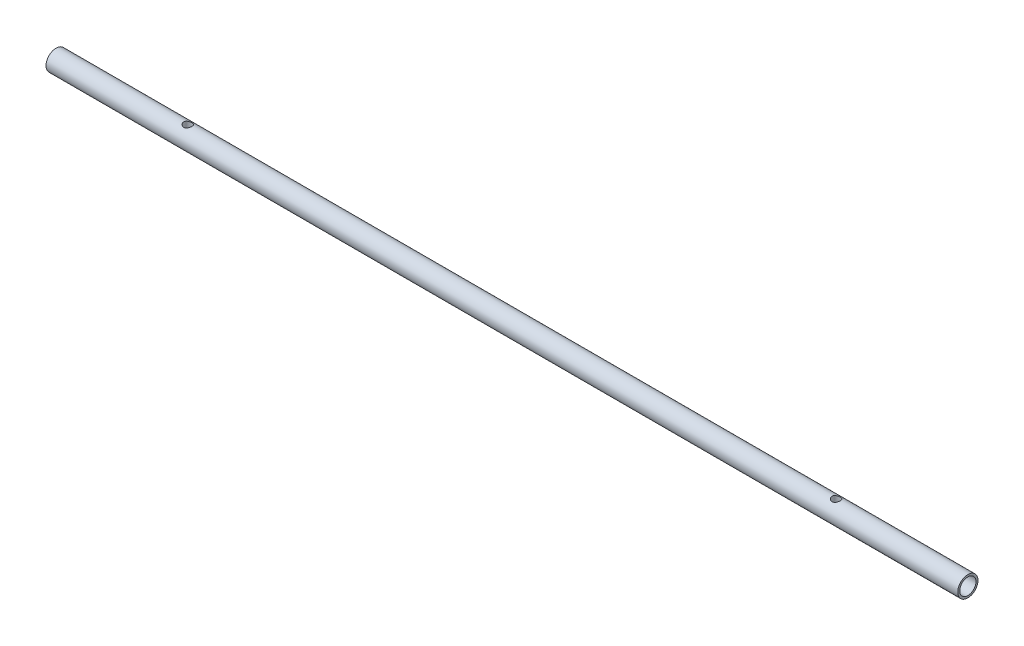
SolidWorks part; units mm, degrees
ref_plane "Front Plane" through (0, 0, 0) normal (1, 0, 0) x (0, 1, 0)
ref_plane "Top Plane" through (0, 0, 0) normal (0, 0, 1) x (0, 1, 0)
ref_plane "Right Plane" through (0, 0, 0) normal (0, 1, 0) x (-1, 0, 0)
sketch "Sketch1" plane through (0, 0, 0) normal (1, 0, 0) x (0, 1, 0)
  circle A0 centre (0, 0) radius 10
  dimension "D1" = 20
extrude "Boss-Extrude1" add sketch "Sketch1" along normal blind 900
sketch "Sketch2" plane through (900, 0, 0) normal (1, 0, 0) x (0, 1, 0)
  circle A0 centre (0, 0) radius 8
  dimension "D1" = 16
extrude "Cut-Extrude1" cut sketch "Sketch2" against normal blind 40
sketch "Sketch3" plane through (0, 0, 0) normal (-1, 0, 0) x (0, -1, 0)
  circle A0 centre (0, 0) radius 8
  dimension "D1" = 16
extrude "Cut-Extrude2" cut sketch "Sketch3" against normal blind 40
sketch "Sketch4" plane through (0, 0, 0) normal (0, 1, 0) x (-1, 0, 0)
  line L0 (-450, 10) -> (-450, -10) construction
  line L1 (0, 10) -> (-900, 10) construction
  line L2 (-900, -10) -> (0, -10) construction
  line L3 (-450, 0) -> (-130, 0) construction
  circle A0 centre (-130, 0) radius 4
  circle A1 centre (-770, 0) radius 4
  dimension "D2" = 8
  dimension "D1" = 320
extrude "Cut-Extrude3" cut sketch "Sketch4" against normal blind 40 and the other way blind 40
